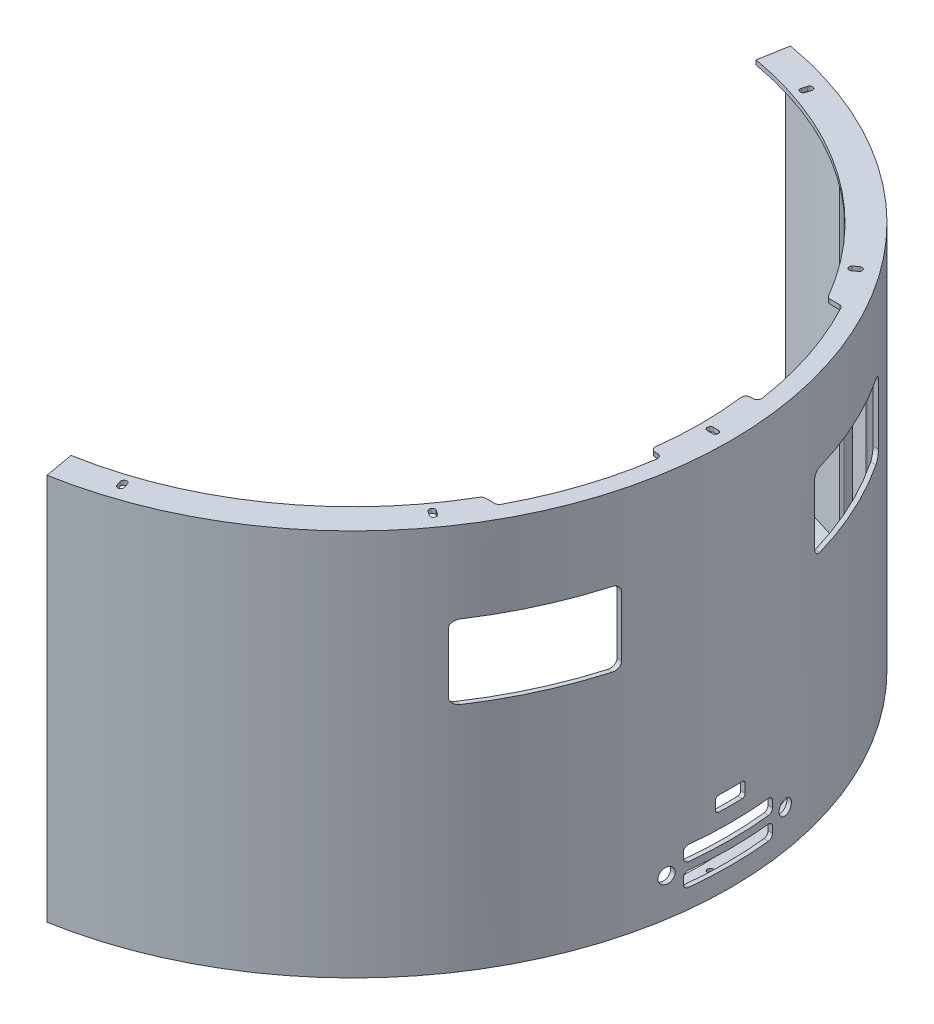
SolidWorks part; units mm, degrees
ref_plane "Front Plane" through (0, 0, 0) normal (0, 0, 1) x (1, 0, 0)
ref_plane "Top Plane" through (0, 0, 0) normal (0, 1, 0) x (1, 0, 0)
ref_plane "Right Plane" through (0, 0, 0) normal (1, 0, 0) x (0, 0, -1)
sketch "Sketch3" plane through (0, 0, 0) normal (0, 1, 0) x (1, 0, 0)
  line L0 (0, -251.5) -> (0, 251.5)
  line L1 (-44.1935, 250.6336) -> (-43.6725, 247.6791)
  line L2 (-43.6725, -247.6791) -> (-44.1935, -250.6336)
  arc A0 (0, 251.5) -> (0, -251.5) centre (0, 0) cw
  arc A1 (0, 251.5) -> (-43.6725, 247.6791) centre (0, 0) ccw
  arc A2 (0, -251.5) -> (-43.6725, -247.6791) centre (0, 0) cw
  arc A3 (0, 254.5) -> (0, -254.5) centre (0, 0) cw
  arc A4 (0, 254.5) -> (-44.1935, 250.6336) centre (0, 0) ccw
  arc A5 (0, -254.5) -> (-44.1935, -250.6336) centre (0, 0) cw
  point P4 (0, 0)
  dimension "D1" = 503
  dimension "D2" = 3
  dimension "D3" = 3
  dimension "D4" = 3
extrude "Boss-Extrude1" add sketch "Sketch3" along normal blind 255 contours A5 A3 A4 L1 A1 A0 A2 L2 region at (252.0902, 0, 0)
sketch "Sketch6" plane through (0, 255, 0) normal (0, 1, 0) x (1, 0, 0)
  line L0 (0, -256) -> (0, 256)
  line L1 (-2, 253.0819) -> (-2, 247.0819)
  line L2 (-1, 246.0819) -> (1, 246.0819)
  line L3 (2, 247.0819) -> (2, 253.0819)
  line L4 (-2, 253.0819) -> (2, 253.0819)
  line L54 (108.0062, 228.8867) -> (105.4029, 223.4809)
  line L55 (105.87, 222.146) -> (107.6719, 221.2783)
  line L56 (109.0068, 221.7454) -> (111.6101, 227.1512)
  line L57 (108.0062, 228.8867) -> (111.6101, 227.1512)
  line L58 (196.6204, 159.3577) -> (191.9294, 155.6167)
  line L59 (191.7711, 154.2114) -> (193.0181, 152.6477)
  line L60 (194.4234, 152.4894) -> (199.1144, 156.2303)
  line L61 (196.6204, 159.3577) -> (199.1144, 156.2303)
  line L62 (246.2916, 58.2659) -> (240.442, 56.9308)
  line L63 (239.6896, 55.7333) -> (240.1347, 53.7835)
  line L64 (241.3321, 53.031) -> (247.1817, 54.3662)
  line L65 (246.2916, 58.2659) -> (247.1817, 54.3662)
  line L66 (247.1817, -54.3662) -> (241.3321, -53.031)
  line L67 (240.1347, -53.7835) -> (239.6896, -55.7333)
  line L68 (240.442, -56.9308) -> (246.2916, -58.2659)
  line L69 (247.1817, -54.3662) -> (246.2916, -58.2659)
  line L70 (199.1144, -156.2303) -> (194.4234, -152.4894)
  line L71 (193.0181, -152.6477) -> (191.7711, -154.2114)
  line L72 (191.9294, -155.6167) -> (196.6204, -159.3577)
  line L73 (199.1144, -156.2303) -> (196.6204, -159.3577)
  line L74 (111.6101, -227.1512) -> (109.0068, -221.7454)
  line L75 (107.6719, -221.2783) -> (105.87, -222.146)
  line L76 (105.4029, -223.4809) -> (108.0062, -228.8867)
  line L77 (111.6101, -227.1512) -> (108.0062, -228.8867)
  line L78 (2, -253.0819) -> (2, -247.0819)
  line L79 (1, -246.0819) -> (-1, -246.0819)
  line L80 (-2, -247.0819) -> (-2, -253.0819)
  line L81 (2, -253.0819) -> (-2, -253.0819)
  arc A2 (2, 247.0819) -> (1, 246.0819) centre (1, 247.0819) cw
  arc A3 (-2, 247.0819) -> (-1, 246.0819) centre (-1, 247.0819) ccw
  arc A26 (109.0068, 221.7454) -> (107.6719, 221.2783) centre (108.1058, 222.1792) cw
  arc A27 (105.4029, 223.4809) -> (105.87, 222.146) centre (106.3039, 223.047) ccw
  arc A28 (194.4234, 152.4894) -> (193.0181, 152.6477) centre (193.7999, 153.2712) cw
  arc A29 (191.9294, 155.6167) -> (191.7711, 154.2114) centre (192.5529, 154.8349) ccw
  arc A30 (241.3321, 53.031) -> (240.1347, 53.7835) centre (241.1096, 54.006) cw
  arc A31 (240.442, 56.9308) -> (239.6896, 55.7333) centre (240.6645, 55.9558) ccw
  arc A32 (240.442, -56.9308) -> (239.6896, -55.7333) centre (240.6645, -55.9558) cw
  arc A33 (241.3321, -53.031) -> (240.1347, -53.7835) centre (241.1096, -54.006) ccw
  arc A34 (191.9294, -155.6167) -> (191.7711, -154.2114) centre (192.5529, -154.8349) cw
  arc A35 (194.4234, -152.4894) -> (193.0181, -152.6477) centre (193.7999, -153.2712) ccw
  arc A36 (105.4029, -223.4809) -> (105.87, -222.146) centre (106.3039, -223.047) cw
  arc A37 (109.0068, -221.7454) -> (107.6719, -221.2783) centre (108.1058, -222.1792) ccw
  arc A38 (-2, -247.0819) -> (-1, -246.0819) centre (-1, -247.0819) cw
  arc A39 (2, -247.0819) -> (1, -246.0819) centre (1, -247.0819) ccw
  point P9 (0, 0)
  point P19 (2, 246.0819)
  point P22 (-2, 246.0819)
  point P23 (0, 246.0819)
  point P59 (0, 0)
  point P68 (0, 0)
  point P76 (0, 0)
  dimension "D3" = 1
  dimension "D1" = 7
  dimension "D2" = 4
  dimension "D4" = 0
  dimension "D5" = 7
  dimension "D6" = 256
  dimension "D7" = 8
extrude "Boss-Extrude2" add sketch "Sketch6" against normal blind 255 separate body contours L3 L4 L1 A3 L2 A2 | L56 L57 L54 A27 L55 A26 | L60 L61 L58 A29 L59 A28 | L64 L65 L62 A31 L63 A30 | L68 L69 L66 A33 L67 A32 | L72 L73 L70 A35 L71 A34 | L76 L77 L74 A37 L75 A36 | L78 A39 L79 A38 L80 L81
combine bodies "Combine2" operation type add bodies to combine 109 101 115 116 117 118 119 120 121
sketch "Sketch7" plane through (0, 255, 0) normal (0, 1, 0) x (1, 0, 0)
  line L0 (-44.1935, 250.6336) -> (-40.7205, 230.9374)
  line L1 (-44.1935, -250.6336) -> (-40.7205, -230.9374)
  arc A0 (-40.7205, 230.9374) -> (-40.7205, -230.9374) centre (0, 0) cw
  arc A2 (-44.1935, 250.6336) -> (-44.1935, -250.6336) centre (0, 0) cw
  arc A3 (-44.1935, -250.6336) -> (-44.1935, 250.6336) centre (0, 0) ccw construction
extrude "Boss-Extrude3" add sketch "Sketch7" along normal blind 3 contours A2 L0 A0 L1 region at (248.5983, 255, 0)
sketch "Sketch8" plane through (0, 255, 0) normal (0, -1, 0) x (1, 0, 0)
  line L0 (240.8, 0) -> (244.2, 0) construction
  line L1 (240.8, 2) -> (244.2, 2)
  line L2 (240.8, -2) -> (244.2, -2)
  line L3 (194.8113, -141.5387) -> (197.562, -143.5372) construction
  line L12 (195.9869, -139.9207) -> (198.7375, -141.9191)
  line L21 (193.6357, -143.1567) -> (196.3864, -145.1552)
  line L24 (74.4113, -229.0144) -> (75.462, -232.248) construction
  line L27 (76.3134, -228.3964) -> (77.3641, -231.63)
  line L28 (72.5092, -229.6324) -> (73.5598, -232.866)
  line L29 (-74.4113, -229.0144) -> (-75.462, -232.248) construction
  line L30 (-72.5092, -229.6324) -> (-73.5598, -232.866)
  line L31 (-76.3134, -228.3964) -> (-77.3641, -231.63)
  line L32 (-194.8113, -141.5387) -> (-197.562, -143.5372) construction
  line L33 (-193.6357, -143.1567) -> (-196.3864, -145.1552)
  line L34 (-195.9869, -139.9207) -> (-198.7375, -141.9191)
  line L35 (-240.8, 0) -> (-244.2, 0) construction
  line L36 (-240.8, -2) -> (-244.2, -2)
  line L37 (-240.8, 2) -> (-244.2, 2)
  line L38 (-194.8113, 141.5387) -> (-197.562, 143.5372) construction
  line L39 (-195.9869, 139.9207) -> (-198.7375, 141.9191)
  line L40 (-193.6357, 143.1567) -> (-196.3864, 145.1552)
  line L41 (-74.4113, 229.0144) -> (-75.462, 232.248) construction
  line L42 (-76.3134, 228.3964) -> (-77.3641, 231.63)
  line L43 (-72.5092, 229.6324) -> (-73.5598, 232.866)
  line L44 (74.4113, 229.0144) -> (75.462, 232.248) construction
  line L45 (72.5092, 229.6324) -> (73.5598, 232.866)
  line L46 (76.3134, 228.3964) -> (77.3641, 231.63)
  line L47 (194.8113, 141.5387) -> (197.562, 143.5372) construction
  line L48 (193.6357, 143.1567) -> (196.3864, 145.1552)
  line L49 (195.9869, 139.9207) -> (198.7375, 141.9191)
  circle A1 centre (242.5, 0) radius 1.7 construction
  arc A2 (240.8, 2) -> (240.8, -2) centre (240.8, 0) ccw
  arc A3 (244.2, -2) -> (244.2, 2) centre (244.2, 0) ccw
  arc A24 (195.9869, -139.9207) -> (193.6357, -143.1567) centre (194.8113, -141.5387) ccw
  arc A25 (196.3864, -145.1552) -> (198.7375, -141.9191) centre (197.562, -143.5372) ccw
  arc A26 (76.3134, -228.3964) -> (72.5092, -229.6324) centre (74.4113, -229.0144) ccw
  arc A27 (73.5598, -232.866) -> (77.3641, -231.63) centre (75.462, -232.248) ccw
  arc A28 (-72.5092, -229.6324) -> (-76.3134, -228.3964) centre (-74.4113, -229.0144) ccw
  arc A29 (-77.3641, -231.63) -> (-73.5598, -232.866) centre (-75.462, -232.248) ccw
  arc A30 (-193.6357, -143.1567) -> (-195.9869, -139.9207) centre (-194.8113, -141.5387) ccw
  arc A31 (-198.7375, -141.9191) -> (-196.3864, -145.1552) centre (-197.562, -143.5372) ccw
  arc A32 (-240.8, -2) -> (-240.8, 2) centre (-240.8, 0) ccw
  arc A33 (-244.2, 2) -> (-244.2, -2) centre (-244.2, 0) ccw
  arc A34 (-195.9869, 139.9207) -> (-193.6357, 143.1567) centre (-194.8113, 141.5387) ccw
  arc A35 (-196.3864, 145.1552) -> (-198.7375, 141.9191) centre (-197.562, 143.5372) ccw
  arc A36 (-76.3134, 228.3964) -> (-72.5092, 229.6324) centre (-74.4113, 229.0144) ccw
  arc A37 (-73.5598, 232.866) -> (-77.3641, 231.63) centre (-75.462, 232.248) ccw
  arc A38 (72.5092, 229.6324) -> (76.3134, 228.3964) centre (74.4113, 229.0144) ccw
  arc A39 (77.3641, 231.63) -> (73.5598, 232.866) centre (75.462, 232.248) ccw
  arc A40 (193.6357, 143.1567) -> (195.9869, 139.9207) centre (194.8113, 141.5387) ccw
  arc A41 (198.7375, 141.9191) -> (196.3864, 145.1552) centre (197.562, 143.5372) ccw
  point P6 (242.5, 0)
  point P16 (196.1866, -142.5379)
  point P23 (74.9366, -230.6312)
  point P28 (0, 0)
  point P31 (-74.9366, -230.6312)
  point P35 (0, 0)
  point P39 (-196.1866, -142.5379)
  point P44 (0, 0)
  point P47 (-242.5, 0)
  point P54 (-196.1866, 142.5379)
  point P57 (0, 0)
  point P62 (-74.9366, 230.6312)
  point P69 (74.9366, 230.6312)
  point P76 (196.1866, 142.5379)
  point P81 (0, 0)
  dimension "D1" = 2
extrude "Cut-Extrude3" cut sketch "Sketch8" against normal blind 5
pattern_linear "LPattern1" count 2 spacing 258 along (0, -1, 0) of "Boss-Extrude3"
pattern_linear "LPattern2" count 2 spacing 258 along (0, -1, 0) of "Cut-Extrude3"
sketch "Sketch11" plane through (0, 258, 0) normal (0, 1, 0) x (1, 0, 0)
  line L0 (-44.1935, 250.6336) -> (0, 0)
  line L1 (0, 0) -> (44.1935, 250.6336)
  line L2 (-117.5787, 0) -> (117.5787, 0) construction
  arc A0 (-44.1935, 250.6336) -> (44.1935, 250.6336) centre (0, 0) cw
extrude "Cut-Extrude7" cut sketch "Sketch11" against normal blind 324
mirror "Mirror1" about plane through (0, 0, 0) normal (0, 0, 1) of "Cut-Extrude7"
sketch "Sketch13" plane through (0, 258, 0) normal (0, 1, 0) x (1, 0, 0)
  line L3 (240.8, 32.1355) -> (189.8429, 32.1355)
  line L4 (189.8429, 32.1355) -> (189.8429, 116.171)
  line L5 (189.8429, 116.171) -> (213.358, 116.171)
  line L6 (-117.5787, 0) -> (117.5787, 0) construction
  line L7 (189.8429, -116.171) -> (213.358, -116.171)
  line L8 (189.8429, -32.1355) -> (189.8429, -116.171)
  line L9 (240.8, -32.1355) -> (189.8429, -32.1355)
  arc A0 (240.8, 32.1355) -> (213.358, 116.171) centre (0, 0) ccw
  arc A1 (240.8, -32.1355) -> (213.358, -116.171) centre (0, 0) cw
extrude "Cut-Extrude10" cut sketch "Sketch13" against normal blind 5
fillet "Fillet2" radius 3 8 edges at (203.7021, 256.5, 116.171) (213.358, 256.5, 116.171) (232.2877, 256.5, 32.1355) (240.8, 256.5, 32.1355) (232.2877, 256.5, -32.1355) (240.8, 256.5, -32.1355) (213.358, 256.5, -116.171) (203.7021, 256.5, -116.171)
sketch "Sketch14" plane through (0, 0, 0) normal (1, 0, 0) x (0, 0, -1)
  line L1 (-140, 153) -> (-70, 153)
  line L2 (-145, 158) -> (-145, 198)
  line L3 (-140, 203) -> (-70, 203)
  line L4 (-65, 158) -> (-65, 198)
  line L5 (-145, 153) -> (-65, 203) construction
  line L6 (-145, 203) -> (-65, 153) construction
  line L8 (-57.9121, 0) -> (-155.2391, 0) construction
  arc A0 (-140, 203) -> (-145, 198) centre (-140, 198) ccw
  arc A1 (-145, 158) -> (-140, 153) centre (-140, 158) ccw
  arc A2 (-70, 153) -> (-65, 158) centre (-70, 158) ccw
  arc A3 (-70, 203) -> (-65, 198) centre (-70, 198) cw
  point P0 (-105, 178)
  point P9 (0, 0)
  dimension "D5" = 5
  dimension "D1" = 80
  dimension "D2" = 50
  dimension "D3" = 178
  dimension "D4" = 105
extrude "Cut-Extrude11" cut sketch "Sketch14" along normal blind 317
mirror "Mirror2" about plane through (0, 0, 0) normal (0, 0, 1) of "Cut-Extrude11"
sketch "Sketch15" plane through (0, 0, 0) normal (1, 0, 0) x (0, 0, -1)
  line L0 (-27, 10) -> (27, 10)
  line L1 (-27, 25) -> (27, 25)
  line L2 (-30, 28) -> (-30, 32)
  line L3 (-27, 35) -> (27, 35)
  line L4 (30, 28) -> (30, 32)
  line L5 (-30, 25) -> (30, 35) construction
  line L6 (-30, 35) -> (30, 25) construction
  line L7 (-30, 13) -> (-30, 17)
  line L8 (-27, 20) -> (27, 20)
  line L9 (30, 13) -> (30, 17)
  line L10 (-30, 10) -> (30, 20) construction
  line L11 (-30, 20) -> (30, 10) construction
  line L12 (0, 117.5787) -> (0, -117.5787) construction
  line L14 (-8, 45) -> (8, 45)
  line L15 (-10, 47) -> (-10, 53)
  line L16 (-8, 55) -> (8, 55)
  line L17 (10, 47) -> (10, 53)
  line L18 (-10, 45) -> (10, 55) construction
  line L19 (-10, 55) -> (10, 45) construction
  arc A0 (-27, 25) -> (-30, 28) centre (-27, 28) cw
  arc A1 (-30, 32) -> (-27, 35) centre (-27, 32) cw
  arc A2 (27, 25) -> (30, 28) centre (27, 28) ccw
  arc A3 (27, 35) -> (30, 32) centre (27, 32) cw
  arc A4 (-27, 10) -> (-30, 13) centre (-27, 13) cw
  arc A5 (-30, 17) -> (-27, 20) centre (-27, 17) cw
  arc A6 (27, 10) -> (30, 13) centre (27, 13) ccw
  arc A7 (27, 20) -> (30, 17) centre (27, 17) cw
  circle A8 centre (40, 22.5) radius 5
  circle A9 centre (-40, 22.5) radius 5
  arc A10 (-8, 45) -> (-10, 47) centre (-8, 47) cw
  arc A11 (-10, 53) -> (-8, 55) centre (-8, 53) cw
  arc A12 (8, 45) -> (10, 47) centre (8, 47) ccw
  arc A13 (8, 55) -> (10, 53) centre (8, 53) cw
  point P0 (0, 30)
  point P20 (0, 15)
  point P41 (0, 50)
  dimension "D5" = 3
  dimension "D8" = 2.5
  dimension "D13" = 2
  dimension "D1" = 60
  dimension "D2" = 0
  dimension "D3" = 30
  dimension "D4" = 10
  dimension "D7" = 15
  dimension "D9" = 40
  dimension "D10" = 10
  dimension "D11" = 20
  dimension "D12" = 20
  dimension "D6" = 2
extrude "Cut-Extrude12" cut sketch "Sketch15" along normal blind 368
